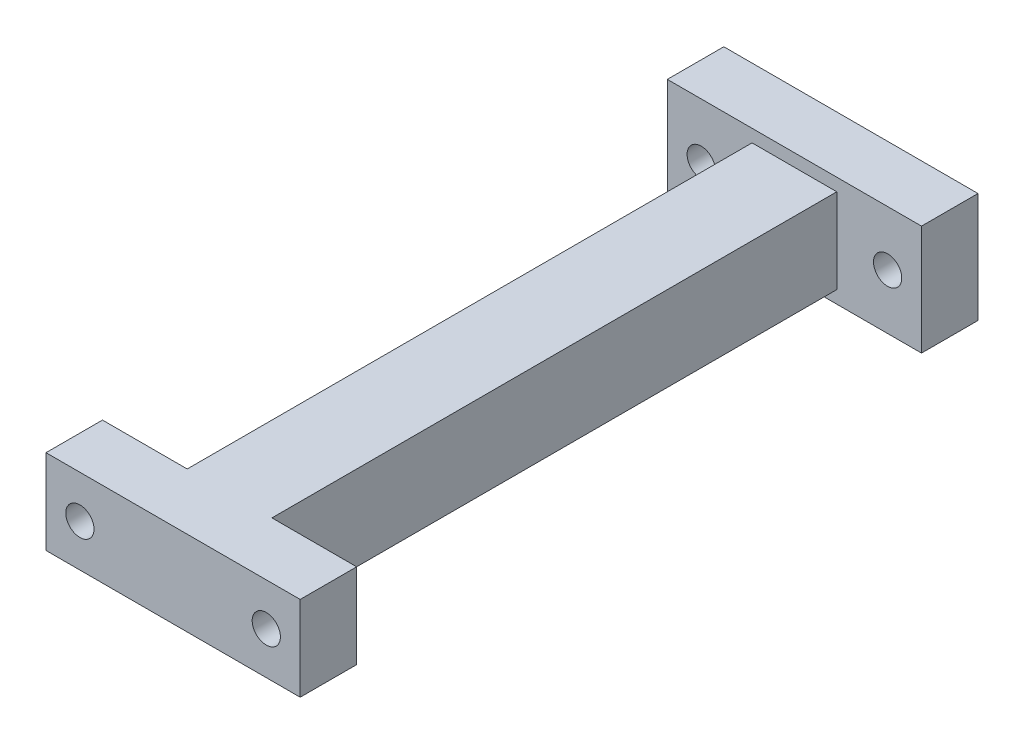
SolidWorks part; units mm, degrees
ref_plane "前视基准面" through (0, 0, 0) normal (0, 0, 1) x (1, 0, 0)
ref_plane "上视基准面" through (0, 0, 0) normal (0, 1, 0) x (1, 0, 0)
ref_plane "右视基准面" through (0, 0, 0) normal (1, 0, 0) x (0, 0, -1)
sketch "草图1" plane through (0, 0, 0) normal (0, 0, 1) x (1, 0, 0)
  line L1 (7.5, -7.5) -> (-7.5, -7.5)
  line L2 (7.5, -7.5) -> (7.5, 7.5)
  line L3 (7.5, 7.5) -> (-7.5, 7.5)
  line L4 (-7.5, -7.5) -> (-7.5, 7.5)
  line L5 (7.5, -7.5) -> (-7.5, 7.5) construction
  line L6 (7.5, 7.5) -> (-7.5, -7.5) construction
  point P0 (0, 0)
  dimension "D1" = 15
  dimension "D2" = 15
extrude "凸台-拉伸1" add sketch "草图1" along normal blind 120
sketch "草图2" plane through (0, 0, 120) normal (0, 0, 1) x (1, 0, 0)
  line L1 (22.5, -7.5) -> (-22.5, -7.5)
  line L2 (22.5, -7.5) -> (22.5, 7.5)
  line L3 (22.5, 7.5) -> (-22.5, 7.5)
  line L4 (-22.5, -7.5) -> (-22.5, 7.5)
  line L5 (22.5, -7.5) -> (-22.5, 7.5) construction
  line L6 (22.5, 7.5) -> (-22.5, -7.5) construction
  point P0 (0, 0)
  dimension "D1" = 15
  dimension "D2" = 45
extrude "凸台-拉伸2" add sketch "草图2" against normal blind 10
sketch "草图3" plane through (0, 0, 120) normal (0, 0, 1) x (1, 0, 0)
  line L0 (-22.5, 7.5) -> (-22.5, -7.5) construction
  line L2 (0, -10.71) -> (0, 10.71) construction
  circle A0 centre (-16.5, 0) radius 2.5
  circle A1 centre (16.5, 0) radius 2.5
  dimension "D1" = 6
  dimension "D2" = 5
extrude "切除-拉伸1" cut sketch "草图3" against normal blind 20
sketch "草图5" plane through (0, 0, 0) normal (0, 0, -1) x (-1, 0, 0)
  line L1 (22.5, -9.7364) -> (-22.5, -9.7364)
  line L2 (22.5, -9.7364) -> (22.5, 9.7364)
  line L3 (22.5, 9.7364) -> (-22.5, 9.7364)
  line L4 (-22.5, -9.7364) -> (-22.5, 9.7364)
  line L5 (22.5, -9.7364) -> (-22.5, 9.7364) construction
  line L6 (22.5, 9.7364) -> (-22.5, -9.7364) construction
  point P0 (0, 0)
  dimension "D1" = 45
extrude "凸台-拉伸3" add sketch "草图5" against normal blind 10
sketch "草图6" plane through (0, 0, 0) normal (0, 0, -1) x (-1, 0, 0)
  line L0 (-22.5, 9.7364) -> (-22.5, -9.7364) construction
  line L1 (22.5, -9.7364) -> (22.5, 9.7364) construction
  circle A0 centre (-16.5, 0) radius 2.5
  circle A1 centre (16.5, 0) radius 2.5
  point P6 (-22.5, 0)
  point P9 (22.5, 0)
  dimension "D1" = 6
  dimension "D3" = 5
  dimension "D4" = 5
  dimension "D2" = 6
extrude "切除-拉伸2" cut sketch "草图6" against normal through all
